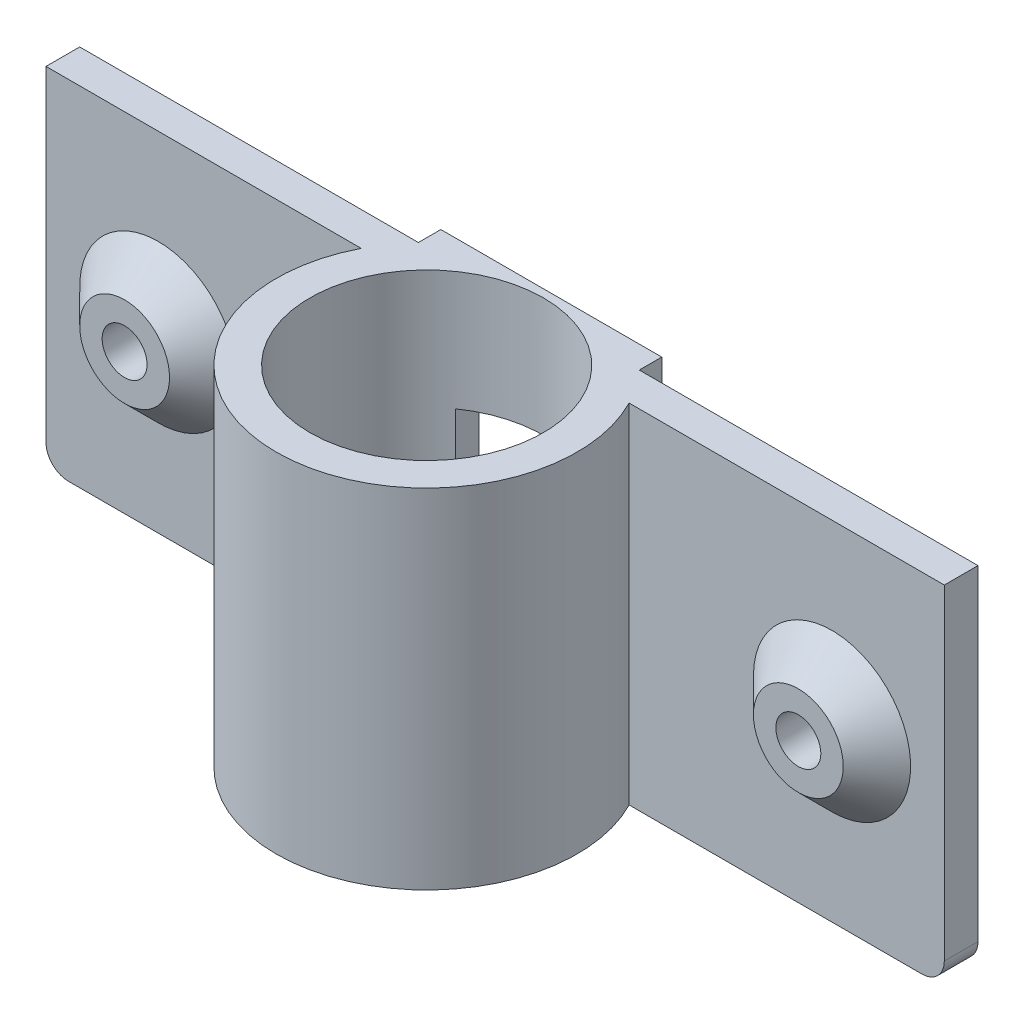
SolidWorks part; units mm, degrees
ref_plane "Front Plane" through (0, 0, 0) normal (0, 0, 1) x (1, 0, 0)
ref_plane "Top Plane" through (0, 0, 0) normal (0, 1, 0) x (1, 0, 0)
ref_plane "Right Plane" through (0, 0, 0) normal (1, 0, 0) x (0, 0, -1)
sketch "Sketch1" plane through (0, 0, 0) normal (0, 1, 0) x (1, 0, 0)
  line L0 (-3.7533, 5.55) -> (3.7533, 5.55)
  line L1 (4.9181, 4.55) -> (20, 4.55)
  line L2 (5.9655, 3.05) -> (20, 3.05)
  line L3 (20, 4.55) -> (20, 3.05)
  line L4 (0, 13.9078) -> (0, -10.692) construction
  line L5 (3.7533, 5.55) -> (4.9181, 5.55)
  line L6 (4.9181, 5.55) -> (4.9181, 4.55)
  line L7 (-5.9655, 3.05) -> (-20, 3.05)
  line L8 (-20, 4.55) -> (-20, 3.05)
  line L9 (-4.9181, 4.55) -> (-20, 4.55)
  line L10 (-4.9181, 5.55) -> (-4.9181, 4.55)
  line L11 (-3.7533, 5.55) -> (-4.9181, 5.55)
  circle A0 centre (0, 0) radius 5.2
  circle A1 centre (0, 0) radius 6.7
  point P6 (0, 5.2)
  dimension "D1" = 10.4
  dimension "D2" = 1.5
  dimension "D3" = 0.35
  dimension "D4" = 1
  dimension "D5" = 1.5
  dimension "D6" = 40
extrude "Base shape" add sketch "Sketch1" along normal blind 14 contours A1 L9 L8 L7 | A1 L11 L10 | L4 L0 A1 A0 | L0 L4 A0 A1 | A1 L6 L5 | A1 L2 L3 L1 region at (-4.5452, 0, -5.2296) region at (-1.8767, 0, -5.4104) region at (1.8767, 0, -5.4104) region at (-12.7433, 0, -3.809) region at (4.5452, 0, -5.2296) region at (12.7433, 0, -3.809)
sketch "Sketch2" plane through (0, 0, 0) normal (0, -1, 0) x (1, 0, 0)
  line L9 (-5.9655, -3.05) -> (-20, -3.05)
  line L10 (-20, -3.05) -> (-20, -4.55)
  line L11 (-20, -4.55) -> (-4.9181, -4.55)
  line L12 (-4.9181, -4.55) -> (-4.9181, -5.55)
  line L13 (-4.9181, -5.55) -> (4.9181, -5.55)
  line L14 (4.9181, -5.55) -> (4.9181, -4.55)
  line L15 (4.9181, -4.55) -> (20, -4.55)
  line L16 (20, -4.55) -> (20, -3.05)
  line L17 (20, -3.05) -> (5.9655, -3.05)
  line L18 (-5.9655, -3.05) -> (-20, -3.05)
  line L19 (-20, -3.05) -> (-20, -4.55)
  line L20 (-20, -4.55) -> (-4.9181, -4.55)
  line L21 (-4.9181, -4.55) -> (-4.9181, -5.55)
  line L22 (-4.9181, -5.55) -> (4.9181, -5.55)
  line L23 (4.9181, -5.55) -> (4.9181, -4.55)
  line L24 (4.9181, -4.55) -> (20, -4.55)
  line L25 (20, -4.55) -> (20, -3.05)
  line L26 (20, -3.05) -> (5.9655, -3.05)
  arc A1 (5.9655, -3.05) -> (-5.9655, -3.05) centre (0, 0) ccw
  arc A2 (5.9655, -3.05) -> (-5.9655, -3.05) centre (0, 0) ccw
  dimension "D1" = 0
extrude "Bottom extrude" add sketch "Sketch2" along normal blind 1.5
sketch "Sketch3" plane through (0, 0, 0) normal (0, 1, 0) x (1, 0, 0)
  circle A0 centre (0, 0) radius 3
  dimension "D1" = 6
extrude "Pin cut" cut sketch "Sketch3" against normal blind 1.2
sketch "Sketch5" plane through (0, 0, -4.55) normal (0, 0, -1) x (-1, 0, 0)
  line L0 (-15, 14) -> (-15, -1.5) construction
  line L1 (-4.9181, 14) -> (-20, 14) construction
  line L2 (-4.9181, -1.5) -> (-20, -1.5) construction
  line L3 (0, 18.7568) -> (0, -7.6861) construction
  circle A0 centre (-15, 6.25) radius 1
  circle A1 centre (15, 6.25) radius 1
  dimension "D2" = 2
  dimension "D1" = 30
extrude "M2 screw holes" cut sketch "Sketch5" against normal up to next
sketch "Sketch6" plane through (0, 0, -3.05) normal (0, 0, 1) x (1, 0, 0)
  line L0 (0, 17.5657) -> (0, -6.5546) construction
  circle A0 centre (-15, 6.25) radius 3.5
  circle A1 centre (-15, 6.25) radius 1 construction
  circle A2 centre (-15, 6.25) radius 1
  circle A3 centre (15, 6.25) radius 3.5
  circle A4 centre (15, 6.25) radius 1
  dimension "D1" = 2.5
extrude "Extra thread extrudes" add sketch "Sketch6" along normal blind 1.5
chamfer "Extra thread chamfers" distance 1.5 angle 45 2 edges at (11.5, 6.25, -1.55) (-11.5, 6.25, -1.55)
sketch "Sketch7" plane through (0, 0, 0) normal (0, 1, 0) x (1, 0, 0)
  circle A0 centre (0, 0) radius 4.05
  circle A1 centre (0, 0) radius 5.2 construction
  circle A3 centre (0, 0) radius 3 construction
  dimension "D2" = 1.05
extrude "Inner bearing free cut" cut sketch "Sketch7" against normal blind 0.5
ref_plane "Bumper plane" through (0, 7, 0) normal (0, 1, 0) x (1, 0, 0)
sketch "Sketch8" plane through (0, 7, 0) normal (0, 1, 0) x (1, 0, 0)
  line L0 (-2.1666, -0.382) -> (-3.2126, 5.55)
  line L1 (0, 15.952) -> (0, -10.9908) construction
  line L2 (2.1666, -0.382) -> (3.2126, 5.55)
  line L3 (-3.2126, 5.55) -> (3.2126, 5.55)
  line L4 (-4.9181, 5.55) -> (4.9181, 5.55) construction
  circle A0 centre (0, 0) radius 2.2
  dimension "D1" = 4.4
  dimension "D2" = 10
extrude "Bumper cut" cut sketch "Sketch8" against normal mid plane 3.4 contours L1 L3 L0 A0 | L3 L1 A0 L2 | A0 L1 | L1 A0 region at (-1.5253, 7, -3.6143) region at (-0.9337, 7, 0) region at (0.9337, 7, 0) region at (1.5253, 7, -3.6143)
fillet "Milled hole fillets" radius 1 4 edges at (-20, -1.5, -3.8) (20, -1.5, -3.8) (-4.9181, -1.5, -5.05) (4.9181, -1.5, -5.05)
